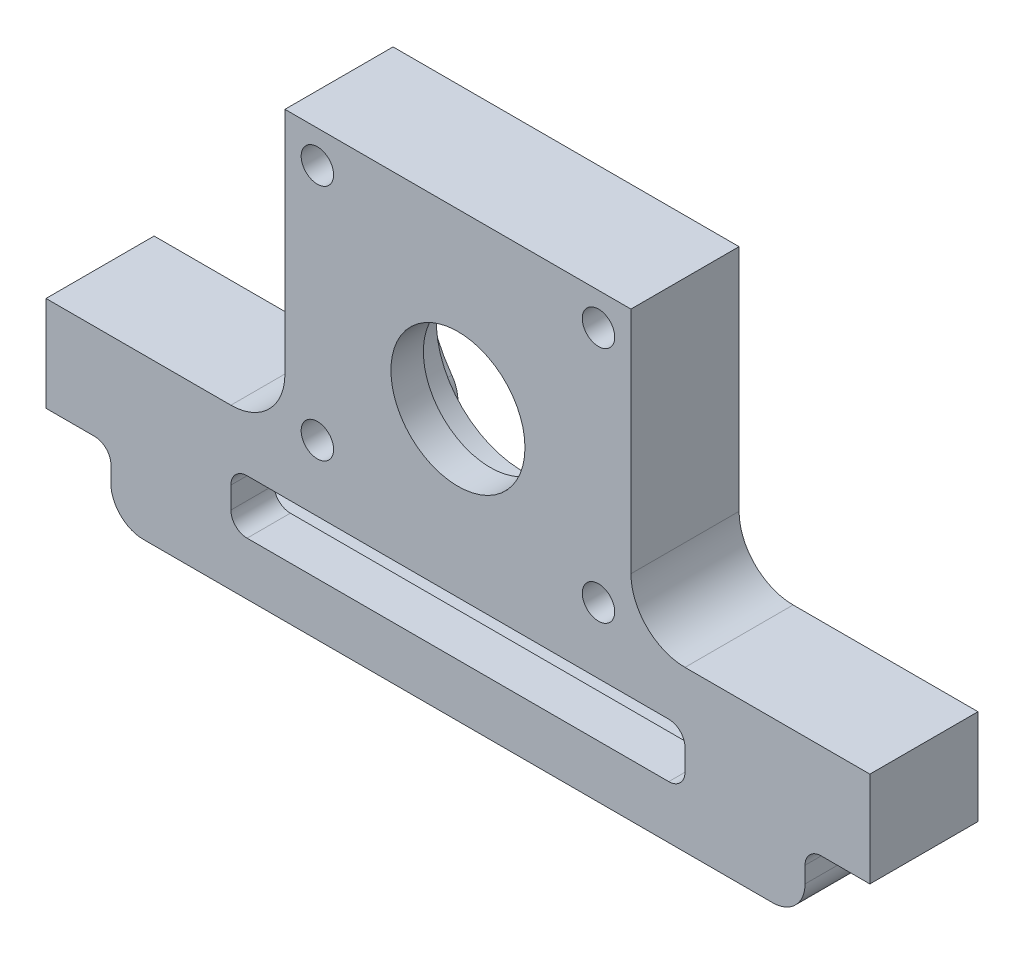
SolidWorks part; units mm, degrees
ref_plane "Front Plane" through (0, 0, 0) normal (0, 0, 1) x (1, 0, 0)
ref_plane "Top Plane" through (0, 0, 0) normal (0, 1, 0) x (1, 0, 0)
ref_plane "Right Plane" through (0, 0, 0) normal (1, 0, 0) x (0, 0, -1)
sketch "Sketch1" plane through (0, 0, 0) normal (0, 0, 1) x (1, 0, 0)
  line L0 (-16, 38) -> (16, 38)
  line L1 (-20.1, 6.5) -> (20.1, 6.5) construction
  line L2 (-20.1, 6.5) -> (-20.1, 2.3) construction
  line L3 (-20.1, 2.3) -> (20.1, 2.3) construction
  line L4 (20.1, 6.5) -> (20.1, 2.3) construction
  line L5 (-20.1, 6.5) -> (20.1, 2.3) construction
  line L6 (-20.1, 2.3) -> (20.1, 6.5) construction
  line L7 (-26.1, 7) -> (26.1, 7) construction
  line L8 (-26.1, 7) -> (-26.1, 1.8) construction
  line L9 (-26.1, 1.8) -> (26.1, 1.8) construction
  line L10 (26.1, 7) -> (26.1, 1.8) construction
  line L11 (-26.1, 7) -> (26.1, 1.8) construction
  line L12 (-26.1, 1.8) -> (26.1, 7) construction
  line L13 (29.1, 9.8) -> (-29.1, 9.8) construction
  line L14 (29.1, 9.8) -> (29.1, -1) construction
  line L15 (29.1, -1) -> (-29.1, -1) construction
  line L16 (-29.1, 9.8) -> (-29.1, -1) construction
  line L17 (29.1, 9.8) -> (-29.1, -1) construction
  line L18 (29.1, -1) -> (-29.1, 9.8) construction
  line L19 (32.1, 11.8) -> (-32.1, 11.8) construction
  line L20 (32.1, 11.8) -> (32.1, -3) construction
  line L21 (32.1, -3) -> (-32.1, -3) construction
  line L22 (-32.1, 11.8) -> (-32.1, -3) construction
  line L23 (32.1, 11.8) -> (-32.1, -3) construction
  line L24 (32.1, -3) -> (-32.1, 11.8) construction
  line L25 (16, 38) -> (16, 11.8)
  line L26 (-16, 38) -> (-16, 11.8)
  line L27 (-16, 11.8) -> (-38.1, 11.8)
  line L28 (-38.1, 11.8) -> (-38.1, 3)
  line L29 (-38.1, 3) -> (-32.1, 3)
  line L30 (-32.1, 3) -> (-32.1, -3)
  line L31 (-32.1, -3) -> (32.1, -3)
  line L32 (32.1, -3) -> (32.1, 3)
  line L33 (32.1, 3) -> (38.1, 3)
  line L34 (38.1, 3) -> (38.1, 11.8)
  line L35 (38.1, 11.8) -> (16, 11.8)
  line L37 (-21, 6.9) -> (21, 6.9)
  line L38 (-21, 6.9) -> (-21, 1.9)
  line L39 (-21, 1.9) -> (21, 1.9)
  line L40 (21, 6.9) -> (21, 1.9)
  line L41 (-21, 6.9) -> (21, 1.9) construction
  line L42 (-21, 1.9) -> (21, 6.9) construction
  circle A0 centre (0, 22) radius 6.2
  circle A1 centre (0, 22) radius 13 construction
  point P2 (0, 4.4)
  point P5 (0, 4.4)
  point P13 (0, 4.4)
  point P18 (0, 4.4)
  point P34 (0, 4.4)
  dimension "D1" = 12.4
  dimension "D11" = 26
  dimension "D2" = 40.2
  dimension "D3" = 4.2
  dimension "D4" = 6
  dimension "D5" = 0.5
  dimension "D6" = 3
  dimension "D7" = 2.8
  dimension "D8" = 3
  dimension "D9" = 2
  dimension "D10" = 3
  dimension "D12" = 22
  dimension "D13" = 16
  dimension "D14" = 32
  dimension "D15" = 16
  dimension "D16" = 6
  dimension "D17" = 42
  dimension "D18" = 5
  dimension "D19" = 6
extrude "Boss-Extrude1" add sketch "Sketch1" along normal blind 10
fillet "Fillet1" radius 1.5 4 edges at (-21, 1.9, 5) (21, 1.9, 5) (21, 6.9, 5) (-21, 6.9, 5)
sketch "Sketch8" plane through (0, 0, 0) normal (0, 0, -1) x (-1, 0, 0)
  circle A0 centre (0, 22) radius 8
  dimension "D1" = 16
extrude "Cut-Extrude9" cut sketch "Sketch8" against normal offset from surface (7 mm away) 3 up to face at (6.2, 22, 10)
sketch "Sketch2" plane through (0, 0, 0) normal (0, 0, 1) x (1, 0, 0)
  circle A0 centre (0, 22) radius 13
  dimension "D1" = 26
extrude "Cut-Extrude1" cut sketch "Sketch2" along normal offset from surface (4 mm away) 6 up to face at (6.2, 22, 10)
sketch "Sketch3" plane through (0, 0, 0) normal (0, 0, 1) x (1, 0, 0)
  line L1 (-29.1, 9.9) -> (29.1, 9.9)
  line L2 (-29.1, 9.9) -> (-29.1, -1.1)
  line L3 (-29.1, -1.1) -> (29.1, -1.1)
  line L4 (29.1, 9.9) -> (29.1, -1.1)
  line L5 (-29.1, 9.9) -> (29.1, -1.1) construction
  line L6 (-29.1, -1.1) -> (29.1, 9.9) construction
  line L7 (0, 6.9) -> (0, 1.9) construction
  line L8 (19.5, 6.9) -> (-19.5, 6.9) construction
  line L9 (-19.5, 1.9) -> (19.5, 1.9) construction
  line L10 (-21, 4.4) -> (21, 4.4) construction
  line L11 (-21, 5.4) -> (-21, 3.4) construction
  line L12 (21, 3.4) -> (21, 5.4) construction
  line L14 (-20.1, 6.5) -> (20.1, 6.5) construction
  line L15 (-20.1, 6.5) -> (-20.1, 2.3) construction
  line L16 (-20.1, 2.3) -> (20.1, 2.3) construction
  line L17 (20.1, 6.5) -> (20.1, 2.3) construction
  line L18 (-20.1, 6.5) -> (20.1, 2.3) construction
  line L19 (-20.1, 2.3) -> (20.1, 6.5) construction
  point P0 (0, 4.4)
  point P17 (0, 4.4)
  dimension "D1" = 4.2
  dimension "D2" = 40.2
  dimension "D3" = 9
  dimension "D4" = 3.4
extrude "Cut-Extrude3" cut sketch "Sketch3" along normal offset from surface (4 mm away) 6 up to face at (6.2, 22, 10)
sketch "Sketch4" plane through (0, 0, 4) normal (0, 0, -1) x (-1, 0, 0)
  line L0 (-29.1, 9.9) -> (-4.7529, 9.9) construction
  line L1 (-26.1, 9.9) -> (26.1, 9.9)
  line L2 (-26.1, 9.9) -> (-26.1, -1.1)
  line L3 (-26.1, -1.1) -> (26.1, -1.1)
  line L4 (26.1, 9.9) -> (26.1, -1.1)
  line L5 (29.1, -1.1) -> (-29.1, -1.1) construction
  line L6 (-29.1, -1.1) -> (-29.1, 9.9) construction
  line L7 (29.1, 9.9) -> (29.1, -1.1) construction
  dimension "D1" = 3
  dimension "D2" = 3
extrude "Cut-Extrude4" cut sketch "Sketch4" against normal blind 2
sketch "Sketch5" plane through (0, 0, 0) normal (0, 0, -1) x (-1, 0, 0)
  line L0 (-16, 38) -> (16, 38) construction
  line L1 (-16, 11.8) -> (-16, 38) construction
  line L2 (16, 38) -> (16, 11.8) construction
  circle A0 centre (-13, 35) radius 1.5
  circle A1 centre (13, 35) radius 1.5
  circle A2 centre (-13, 13) radius 1.5
  circle A3 centre (13, 13) radius 1.5
  dimension "D1" = 3
  dimension "D5" = 25
  dimension "D2" = 3
  dimension "D3" = 3
  dimension "D4" = 3
extrude "Cut-Extrude7" cut sketch "Sketch5" against normal up to next
sketch "Sketch7" plane through (0, 0, 0) normal (0, 0, -1) x (-1, 0, 0)
  line L0 (26.1, 9.9) -> (-26.1, 9.9) construction
  line L1 (-10, 9.9) -> (10, 9.9)
  line L2 (-10, 9.9) -> (-10, 13.6934)
  line L3 (-10, 13.6934) -> (10, 13.6934)
  line L4 (10, 9.9) -> (10, 13.6934)
  line L5 (-16, 11.8) -> (-16, 38) construction
  line L6 (16, 38) -> (16, 11.8) construction
  circle A0 centre (0, 22) radius 13 construction
  dimension "D1" = 6
  dimension "D2" = 6
extrude "Cut-Extrude8" cut sketch "Sketch7" against normal up to surface (4 mm away) up to face at (8, 22, 4)
fillet "Fillet2" radius 1.5 8 edges at (-26.1, -1.1, 5) (-29.1, -1.1, 2) (-29.1, 9.9, 2) (-26.1, 9.9, 5) (26.1, -1.1, 5) (29.1, -1.1, 2) (26.1, 9.9, 5) (29.1, 9.9, 2)
fillet "Fillet3" radius 3 6 edges at (-32.1, -3, 5) (32.1, -3, 5) (10, 13.6934, 2) (-10, 13.6934, 2) (-10, 9.9, 2) (10, 9.9, 2)
fillet "Fillet4" radius 1.5 2 edges at (-32.1, 3, 5) (32.1, 3, 5)
fillet "Fillet5" radius 5 2 edges at (-16, 11.8, 5) (16, 11.8, 5)
